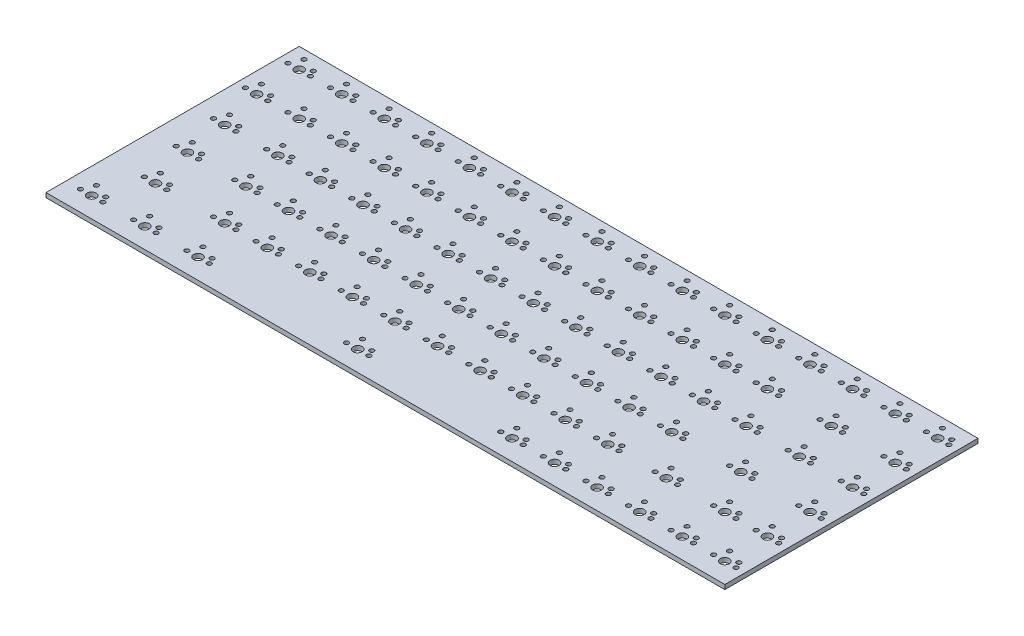
SolidWorks part; units mm, degrees
ref_plane "Спереди" through (0, 0, 0) normal (0, 0, 1) x (1, 0, 0)
ref_plane "Сверху" through (0, 0, 0) normal (0, 1, 0) x (1, 0, 0)
ref_plane "Справа" through (0, 0, 0) normal (1, 0, 0) x (0, 0, -1)
sketch "Эскиз1" plane through (0, 0, 0) normal (0, 1, 0) x (1, 0, 0)
  line L1 (-9, 9) -> (294, 9)
  line L2 (-9, 9) -> (-9, -104)
  line L3 (-9, -104) -> (294, -104)
  line L4 (294, 9) -> (294, -104)
  circle A0 centre (-2.8676, 5) radius 1
  circle A6 centre (0, 0) radius 2
  circle A7 centre (-5, 0) radius 1
  circle A8 centre (5, 0) radius 1
  circle A9 centre (3.65, 2.6) radius 1
  circle A10 centre (16.1324, 5) radius 1
  circle A11 centre (19, 0) radius 2
  circle A12 centre (14, 0) radius 1
  circle A13 centre (24, 0) radius 1
  circle A14 centre (22.65, 2.6) radius 1
  circle A15 centre (16.1324, -14) radius 1
  circle A16 centre (19, -19) radius 2
  circle A17 centre (14, -19) radius 1
  circle A18 centre (24, -19) radius 1
  circle A19 centre (22.65, -16.4) radius 1
  circle A20 centre (-2.8676, -14) radius 1
  circle A21 centre (0, -19) radius 2
  circle A22 centre (-5, -19) radius 1
  circle A23 centre (5, -19) radius 1
  circle A24 centre (3.65, -16.4) radius 1
  circle A25 centre (35.1324, 5) radius 1
  circle A26 centre (38, 0) radius 2
  circle A27 centre (33, 0) radius 1
  circle A28 centre (43, 0) radius 1
  circle A29 centre (41.65, 2.6) radius 1
  circle A30 centre (35.1324, -14) radius 1
  circle A31 centre (38, -19) radius 2
  circle A32 centre (33, -19) radius 1
  circle A33 centre (43, -19) radius 1
  circle A34 centre (41.65, -16.4) radius 1
  circle A35 centre (54.1324, 5) radius 1
  circle A36 centre (57, 0) radius 2
  circle A37 centre (52, 0) radius 1
  circle A38 centre (62, 0) radius 1
  circle A39 centre (60.65, 2.6) radius 1
  circle A40 centre (54.1324, -14) radius 1
  circle A41 centre (57, -19) radius 2
  circle A42 centre (52, -19) radius 1
  circle A43 centre (62, -19) radius 1
  circle A44 centre (60.65, -16.4) radius 1
  circle A45 centre (73.1324, 5) radius 1
  circle A46 centre (76, 0) radius 2
  circle A47 centre (71, 0) radius 1
  circle A48 centre (81, 0) radius 1
  circle A49 centre (79.65, 2.6) radius 1
  circle A50 centre (92.1324, 5) radius 1
  circle A51 centre (95, 0) radius 2
  circle A52 centre (90, 0) radius 1
  circle A53 centre (100, 0) radius 1
  circle A54 centre (98.65, 2.6) radius 1
  circle A55 centre (111.1324, 5) radius 1
  circle A56 centre (114, 0) radius 2
  circle A57 centre (109, 0) radius 1
  circle A58 centre (119, 0) radius 1
  circle A59 centre (117.65, 2.6) radius 1
  circle A60 centre (130.1324, 5) radius 1
  circle A61 centre (133, 0) radius 2
  circle A62 centre (128, 0) radius 1
  circle A63 centre (138, 0) radius 1
  circle A64 centre (136.65, 2.6) radius 1
  circle A65 centre (149.1324, 5) radius 1
  circle A66 centre (152, 0) radius 2
  circle A67 centre (147, 0) radius 1
  circle A68 centre (157, 0) radius 1
  circle A69 centre (155.65, 2.6) radius 1
  circle A70 centre (168.1324, 5) radius 1
  circle A71 centre (171, 0) radius 2
  circle A72 centre (166, 0) radius 1
  circle A73 centre (176, 0) radius 1
  circle A74 centre (174.65, 2.6) radius 1
  circle A75 centre (187.1324, 5) radius 1
  circle A76 centre (190, 0) radius 2
  circle A77 centre (185, 0) radius 1
  circle A78 centre (195, 0) radius 1
  circle A79 centre (193.65, 2.6) radius 1
  circle A80 centre (187.1324, -14) radius 1
  circle A81 centre (190, -19) radius 2
  circle A82 centre (185, -19) radius 1
  circle A83 centre (195, -19) radius 1
  circle A84 centre (193.65, -16.4) radius 1
  circle A85 centre (168.1324, -14) radius 1
  circle A86 centre (171, -19) radius 2
  circle A87 centre (166, -19) radius 1
  circle A88 centre (176, -19) radius 1
  circle A89 centre (174.65, -16.4) radius 1
  circle A90 centre (149.1324, -14) radius 1
  circle A91 centre (152, -19) radius 2
  circle A92 centre (147, -19) radius 1
  circle A93 centre (157, -19) radius 1
  circle A94 centre (155.65, -16.4) radius 1
  circle A95 centre (130.1324, -14) radius 1
  circle A96 centre (133, -19) radius 2
  circle A97 centre (128, -19) radius 1
  circle A98 centre (138, -19) radius 1
  circle A99 centre (136.65, -16.4) radius 1
  circle A100 centre (111.1324, -14) radius 1
  circle A101 centre (114, -19) radius 2
  circle A102 centre (109, -19) radius 1
  circle A103 centre (119, -19) radius 1
  circle A104 centre (117.65, -16.4) radius 1
  circle A105 centre (92.1324, -14) radius 1
  circle A106 centre (95, -19) radius 2
  circle A107 centre (90, -19) radius 1
  circle A108 centre (100, -19) radius 1
  circle A109 centre (98.65, -16.4) radius 1
  circle A110 centre (73.1324, -14) radius 1
  circle A111 centre (76, -19) radius 2
  circle A112 centre (71, -19) radius 1
  circle A113 centre (81, -19) radius 1
  circle A114 centre (79.65, -16.4) radius 1
  circle A115 centre (196.6324, -33) radius 1
  circle A116 centre (199.5, -38) radius 2
  circle A117 centre (194.5, -38) radius 1
  circle A118 centre (204.5, -38) radius 1
  circle A119 centre (203.15, -35.4) radius 1
  circle A120 centre (177.6324, -33) radius 1
  circle A121 centre (180.5, -38) radius 2
  circle A122 centre (175.5, -38) radius 1
  circle A123 centre (185.5, -38) radius 1
  circle A124 centre (184.15, -35.4) radius 1
  circle A125 centre (158.6324, -33) radius 1
  circle A126 centre (161.5, -38) radius 2
  circle A127 centre (156.5, -38) radius 1
  circle A128 centre (166.5, -38) radius 1
  circle A129 centre (165.15, -35.4) radius 1
  circle A130 centre (139.6324, -33) radius 1
  circle A131 centre (142.5, -38) radius 2
  circle A132 centre (137.5, -38) radius 1
  circle A133 centre (147.5, -38) radius 1
  circle A134 centre (146.15, -35.4) radius 1
  circle A135 centre (120.6324, -33) radius 1
  circle A136 centre (123.5, -38) radius 2
  circle A137 centre (118.5, -38) radius 1
  circle A138 centre (128.5, -38) radius 1
  circle A139 centre (127.15, -35.4) radius 1
  circle A140 centre (101.6324, -33) radius 1
  circle A141 centre (104.5, -38) radius 2
  circle A142 centre (99.5, -38) radius 1
  circle A143 centre (109.5, -38) radius 1
  circle A144 centre (108.15, -35.4) radius 1
  circle A145 centre (82.6324, -33) radius 1
  circle A146 centre (85.5, -38) radius 2
  circle A147 centre (80.5, -38) radius 1
  circle A148 centre (90.5, -38) radius 1
  circle A149 centre (89.15, -35.4) radius 1
  circle A150 centre (63.6324, -33) radius 1
  circle A151 centre (66.5, -38) radius 2
  circle A152 centre (61.5, -38) radius 1
  circle A153 centre (71.5, -38) radius 1
  circle A154 centre (70.15, -35.4) radius 1
  circle A155 centre (44.6324, -33) radius 1
  circle A156 centre (47.5, -38) radius 2
  circle A157 centre (42.5, -38) radius 1
  circle A158 centre (52.5, -38) radius 1
  circle A159 centre (51.15, -35.4) radius 1
  circle A160 centre (25.6324, -33) radius 1
  circle A161 centre (28.5, -38) radius 2
  circle A162 centre (23.5, -38) radius 1
  circle A163 centre (33.5, -38) radius 1
  circle A164 centre (32.15, -35.4) radius 1
  circle A165 centre (1.8824, -33) radius 1
  circle A166 centre (4.75, -38) radius 2
  circle A167 centre (-0.25, -38) radius 1
  circle A168 centre (9.75, -38) radius 1
  circle A169 centre (8.4, -35.4) radius 1
  circle A170 centre (4.2574, -52) radius 1
  circle A171 centre (7.125, -57) radius 2
  circle A172 centre (2.125, -57) radius 1
  circle A173 centre (12.125, -57) radius 1
  circle A174 centre (10.775, -54.4) radius 1
  circle A175 centre (30.3824, -52) radius 1
  circle A176 centre (33.25, -57) radius 2
  circle A177 centre (28.25, -57) radius 1
  circle A178 centre (38.25, -57) radius 1
  circle A179 centre (36.9, -54.4) radius 1
  circle A180 centre (49.3824, -52) radius 1
  circle A181 centre (52.25, -57) radius 2
  circle A182 centre (47.25, -57) radius 1
  circle A183 centre (57.25, -57) radius 1
  circle A184 centre (55.9, -54.4) radius 1
  circle A185 centre (68.3824, -52) radius 1
  circle A186 centre (71.25, -57) radius 2
  circle A187 centre (66.25, -57) radius 1
  circle A188 centre (76.25, -57) radius 1
  circle A189 centre (74.9, -54.4) radius 1
  circle A190 centre (87.3824, -52) radius 1
  circle A191 centre (90.25, -57) radius 2
  circle A192 centre (85.25, -57) radius 1
  circle A193 centre (95.25, -57) radius 1
  circle A194 centre (93.9, -54.4) radius 1
  circle A195 centre (106.3824, -52) radius 1
  circle A196 centre (109.25, -57) radius 2
  circle A197 centre (104.25, -57) radius 1
  circle A198 centre (114.25, -57) radius 1
  circle A199 centre (112.9, -54.4) radius 1
  circle A200 centre (125.3824, -52) radius 1
  circle A201 centre (128.25, -57) radius 2
  circle A202 centre (123.25, -57) radius 1
  circle A203 centre (133.25, -57) radius 1
  circle A204 centre (131.9, -54.4) radius 1
  circle A205 centre (144.3824, -52) radius 1
  circle A206 centre (147.25, -57) radius 2
  circle A207 centre (142.25, -57) radius 1
  circle A208 centre (152.25, -57) radius 1
  circle A209 centre (150.9, -54.4) radius 1
  circle A210 centre (163.3824, -52) radius 1
  circle A211 centre (166.25, -57) radius 2
  circle A212 centre (161.25, -57) radius 1
  circle A213 centre (171.25, -57) radius 1
  circle A214 centre (169.9, -54.4) radius 1
  circle A215 centre (182.3824, -52) radius 1
  circle A216 centre (185.25, -57) radius 2
  circle A217 centre (180.25, -57) radius 1
  circle A218 centre (190.25, -57) radius 1
  circle A219 centre (188.9, -54.4) radius 1
  circle A220 centre (201.3824, -52) radius 1
  circle A221 centre (204.25, -57) radius 2
  circle A222 centre (199.25, -57) radius 1
  circle A223 centre (209.25, -57) radius 1
  circle A224 centre (207.9, -54.4) radius 1
  circle A225 centre (191.8824, -71) radius 1
  circle A226 centre (194.75, -76) radius 2
  circle A227 centre (189.75, -76) radius 1
  circle A228 centre (199.75, -76) radius 1
  circle A229 centre (198.4, -73.4) radius 1
  circle A230 centre (172.8824, -71) radius 1
  circle A231 centre (175.75, -76) radius 2
  circle A232 centre (170.75, -76) radius 1
  circle A233 centre (180.75, -76) radius 1
  circle A234 centre (179.4, -73.4) radius 1
  circle A235 centre (153.8824, -71) radius 1
  circle A236 centre (156.75, -76) radius 2
  circle A237 centre (151.75, -76) radius 1
  circle A238 centre (161.75, -76) radius 1
  circle A239 centre (160.4, -73.4) radius 1
  circle A240 centre (134.8824, -71) radius 1
  circle A241 centre (137.75, -76) radius 2
  circle A242 centre (132.75, -76) radius 1
  circle A243 centre (142.75, -76) radius 1
  circle A244 centre (141.4, -73.4) radius 1
  circle A245 centre (115.8824, -71) radius 1
  circle A246 centre (118.75, -76) radius 2
  circle A247 centre (113.75, -76) radius 1
  circle A248 centre (123.75, -76) radius 1
  circle A249 centre (122.4, -73.4) radius 1
  circle A250 centre (96.8824, -71) radius 1
  circle A251 centre (99.75, -76) radius 2
  circle A252 centre (94.75, -76) radius 1
  circle A253 centre (104.75, -76) radius 1
  circle A254 centre (103.4, -73.4) radius 1
  circle A255 centre (77.8824, -71) radius 1
  circle A256 centre (80.75, -76) radius 2
  circle A257 centre (75.75, -76) radius 1
  circle A258 centre (85.75, -76) radius 1
  circle A259 centre (84.4, -73.4) radius 1
  circle A260 centre (58.8824, -71) radius 1
  circle A261 centre (61.75, -76) radius 2
  circle A262 centre (56.75, -76) radius 1
  circle A263 centre (66.75, -76) radius 1
  circle A264 centre (65.4, -73.4) radius 1
  circle A265 centre (39.8824, -71) radius 1
  circle A266 centre (42.75, -76) radius 2
  circle A267 centre (37.75, -76) radius 1
  circle A268 centre (47.75, -76) radius 1
  circle A269 centre (46.4, -73.4) radius 1
  circle A270 centre (9.0074, -71) radius 1
  circle A271 centre (11.875, -76) radius 2
  circle A272 centre (6.875, -76) radius 1
  circle A273 centre (16.875, -76) radius 1
  circle A274 centre (15.525, -73.4) radius 1
  circle A275 centre (206.1324, 5) radius 1
  circle A276 centre (209, 0) radius 2
  circle A277 centre (204, 0) radius 1
  circle A278 centre (214, 0) radius 1
  circle A279 centre (212.65, 2.6) radius 1
  circle A280 centre (225.1324, 5) radius 1
  circle A281 centre (228, 0) radius 2
  circle A282 centre (223, 0) radius 1
  circle A283 centre (233, 0) radius 1
  circle A284 centre (231.65, 2.6) radius 1
  circle A285 centre (244.1324, 5) radius 1
  circle A286 centre (247, 0) radius 2
  circle A287 centre (242, 0) radius 1
  circle A288 centre (252, 0) radius 1
  circle A289 centre (250.65, 2.6) radius 1
  circle A290 centre (263.1324, 5) radius 1
  circle A291 centre (266, 0) radius 2
  circle A292 centre (261, 0) radius 1
  circle A293 centre (271, 0) radius 1
  circle A294 centre (269.65, 2.6) radius 1
  circle A295 centre (282.1324, 5) radius 1
  circle A296 centre (285, 0) radius 2
  circle A297 centre (280, 0) radius 1
  circle A298 centre (290, 0) radius 1
  circle A299 centre (288.65, 2.6) radius 1
  circle A300 centre (282.1324, -14) radius 1
  circle A301 centre (285, -19) radius 2
  circle A302 centre (280, -19) radius 1
  circle A303 centre (290, -19) radius 1
  circle A304 centre (288.65, -16.4) radius 1
  circle A305 centre (253.6324, -14) radius 1
  circle A306 centre (256.5, -19) radius 2
  circle A307 centre (251.5, -19) radius 1
  circle A308 centre (261.5, -19) radius 1
  circle A309 centre (260.15, -16.4) radius 1
  circle A310 centre (225.1324, -14) radius 1
  circle A311 centre (228, -19) radius 2
  circle A312 centre (223, -19) radius 1
  circle A313 centre (233, -19) radius 1
  circle A314 centre (231.65, -16.4) radius 1
  circle A315 centre (206.1324, -14) radius 1
  circle A316 centre (209, -19) radius 2
  circle A317 centre (204, -19) radius 1
  circle A318 centre (214, -19) radius 1
  circle A319 centre (212.65, -16.4) radius 1
  circle A320 centre (215.6324, -33) radius 1
  circle A321 centre (218.5, -38) radius 2
  circle A322 centre (213.5, -38) radius 1
  circle A323 centre (223.5, -38) radius 1
  circle A324 centre (222.15, -35.4) radius 1
  circle A325 centre (234.6324, -33) radius 1
  circle A326 centre (237.5, -38) radius 2
  circle A327 centre (232.5, -38) radius 1
  circle A328 centre (242.5, -38) radius 1
  circle A329 centre (241.15, -35.4) radius 1
  circle A330 centre (258.3824, -33) radius 1
  circle A331 centre (261.25, -38) radius 2
  circle A332 centre (256.25, -38) radius 1
  circle A333 centre (266.25, -38) radius 1
  circle A334 centre (264.9, -35.4) radius 1
  circle A335 centre (282.1324, -33) radius 1
  circle A336 centre (285, -38) radius 2
  circle A337 centre (280, -38) radius 1
  circle A338 centre (290, -38) radius 1
  circle A339 centre (288.65, -35.4) radius 1
  circle A340 centre (282.1324, -52) radius 1
  circle A341 centre (285, -57) radius 2
  circle A342 centre (280, -57) radius 1
  circle A343 centre (290, -57) radius 1
  circle A344 centre (288.65, -54.4) radius 1
  circle A345 centre (251.2574, -52) radius 1
  circle A346 centre (254.125, -57) radius 2
  circle A347 centre (249.125, -57) radius 1
  circle A348 centre (259.125, -57) radius 1
  circle A349 centre (257.775, -54.4) radius 1
  circle A350 centre (220.3824, -52) radius 1
  circle A351 centre (223.25, -57) radius 2
  circle A352 centre (218.25, -57) radius 1
  circle A353 centre (228.25, -57) radius 1
  circle A354 centre (226.9, -54.4) radius 1
  circle A355 centre (210.8824, -71) radius 1
  circle A356 centre (213.75, -76) radius 2
  circle A357 centre (208.75, -76) radius 1
  circle A358 centre (218.75, -76) radius 1
  circle A359 centre (217.4, -73.4) radius 1
  circle A360 centre (237.0074, -71) radius 1
  circle A361 centre (239.875, -76) radius 2
  circle A362 centre (234.875, -76) radius 1
  circle A363 centre (244.875, -76) radius 1
  circle A364 centre (243.525, -73.4) radius 1
  circle A365 centre (263.1324, -71) radius 1
  circle A366 centre (266, -76) radius 2
  circle A367 centre (261, -76) radius 1
  circle A368 centre (271, -76) radius 1
  circle A369 centre (269.65, -73.4) radius 1
  circle A370 centre (282.1324, -71) radius 1
  circle A371 centre (285, -76) radius 2
  circle A372 centre (280, -76) radius 1
  circle A373 centre (290, -76) radius 1
  circle A374 centre (288.65, -73.4) radius 1
  circle A375 centre (282.1324, -90) radius 1
  circle A376 centre (285, -95) radius 2
  circle A377 centre (280, -95) radius 1
  circle A378 centre (290, -95) radius 1
  circle A379 centre (288.65, -92.4) radius 1
  circle A380 centre (263.1324, -90) radius 1
  circle A381 centre (266, -95) radius 2
  circle A382 centre (261, -95) radius 1
  circle A383 centre (271, -95) radius 1
  circle A384 centre (269.65, -92.4) radius 1
  circle A385 centre (244.1324, -90) radius 1
  circle A386 centre (247, -95) radius 2
  circle A387 centre (242, -95) radius 1
  circle A388 centre (252, -95) radius 1
  circle A389 centre (250.65, -92.4) radius 1
  circle A390 centre (225.1324, -90) radius 1
  circle A391 centre (228, -95) radius 2
  circle A392 centre (223, -95) radius 1
  circle A393 centre (233, -95) radius 1
  circle A394 centre (231.65, -92.4) radius 1
  circle A395 centre (206.1324, -90) radius 1
  circle A396 centre (209, -95) radius 2
  circle A397 centre (204, -95) radius 1
  circle A398 centre (214, -95) radius 1
  circle A399 centre (212.65, -92.4) radius 1
  circle A400 centre (187.1324, -90) radius 1
  circle A401 centre (190, -95) radius 2
  circle A402 centre (185, -95) radius 1
  circle A403 centre (195, -95) radius 1
  circle A404 centre (193.65, -92.4) radius 1
  circle A405 centre (47.0074, -90) radius 1
  circle A406 centre (49.875, -95) radius 2
  circle A407 centre (44.875, -95) radius 1
  circle A408 centre (54.875, -95) radius 1
  circle A409 centre (53.525, -92.4) radius 1
  circle A410 centre (23.2574, -90) radius 1
  circle A411 centre (26.125, -95) radius 2
  circle A412 centre (21.125, -95) radius 1
  circle A413 centre (31.125, -95) radius 1
  circle A414 centre (29.775, -92.4) radius 1
  circle A415 centre (-0.4926, -90) radius 1
  circle A416 centre (2.375, -95) radius 2
  circle A417 centre (-2.625, -95) radius 1
  circle A418 centre (7.375, -95) radius 1
  circle A419 centre (6.025, -92.4) radius 1
  circle A420 centre (118.2574, -90) radius 1
  circle A421 centre (121.125, -95) radius 2
  circle A422 centre (116.125, -95) radius 1
  circle A423 centre (126.125, -95) radius 1
  circle A424 centre (124.775, -92.4) radius 1
  point P0 (0, 0)
  point P1 (266, -19)
  point P3 (247, -19)
  point P5 (19, 0)
  point P6 (38, 0)
  point P7 (57, 0)
  point P8 (76, 0)
  point P9 (95, 0)
  point P10 (114, 0)
  point P11 (133, 0)
  point P12 (152, 0)
  point P13 (171, 0)
  point P14 (190, 0)
  point P15 (209, 0)
  point P16 (228, 0)
  point P17 (247, 0)
  point P18 (266, 0)
  point P19 (285, 0)
  point P20 (19, -19)
  point P21 (38, -19)
  point P22 (57, -19)
  point P23 (76, -19)
  point P24 (95, -19)
  point P25 (114, -19)
  point P26 (133, -19)
  point P27 (152, -19)
  point P28 (171, -19)
  point P29 (190, -19)
  point P30 (209, -19)
  point P31 (228, -19)
  point P32 (266, -76)
  point P33 (285, -38)
  point P34 (285, -19)
  point P35 (0, -19)
  point P36 (285, -57)
  point P37 (285, -76)
  point P38 (285, -95)
  point P39 (266, -95)
  point P40 (247, -95)
  point P41 (228, -95)
  point P42 (209, -95)
  point P43 (190, -95)
  point P47 (4.75, -38)
  point P48 (7.125, -57)
  point P49 (11.875, -76)
  point P50 (2.375, -95)
  point P51 (42.75, -76)
  point P52 (26.125, -95)
  point P53 (49.875, -95)
  point P54 (33.25, -57)
  point P55 (28.5, -38)
  point P56 (261.25, -38)
  point P57 (61.75, -76)
  point P58 (47.5, -38)
  point P59 (66.5, -38)
  point P60 (85.5, -38)
  point P61 (104.5, -38)
  point P62 (123.5, -38)
  point P63 (142.5, -38)
  point P64 (161.5, -38)
  point P65 (180.5, -38)
  point P66 (199.5, -38)
  point P67 (218.5, -38)
  point P68 (237.5, -38)
  point P69 (52.25, -57)
  point P70 (71.25, -57)
  point P71 (90.25, -57)
  point P72 (109.25, -57)
  point P73 (128.25, -57)
  point P74 (147.25, -57)
  point P75 (166.25, -57)
  point P76 (185.25, -57)
  point P77 (204.25, -57)
  point P78 (223.25, -57)
  point P79 (80.75, -76)
  point P80 (99.75, -76)
  point P81 (118.75, -76)
  point P82 (137.75, -76)
  point P83 (156.75, -76)
  point P84 (175.75, -76)
  point P85 (194.75, -76)
  point P86 (213.75, -76)
  point P87 (254.125, -57)
  point P88 (239.875, -76)
  point P89 (256.5, -19)
  point P90 (121.125, -95)
  dimension "D6" = 19
  dimension "D7" = 113
  dimension "D8" = 19
  dimension "D9" = 9
  dimension "D10" = 9
  dimension "D11" = 303
  dimension "D12" = 13.75
  dimension "D13" = 16.125
  dimension "D14" = 20.875
  dimension "D15" = 11.375
  dimension "D17" = 23.75
  dimension "D18" = 26.125
  dimension "D19" = 30.875
  dimension "D23" = 23.75
  dimension "D24" = 23.75
  dimension "D25" = 71.25
  dimension "D26" = 28
  dimension "D27" = 9
  dimension "D28" = 9
  dimension "D29" = 9
  dimension "D30" = 28.5
  dimension "D31" = 23.75
  dimension "D32" = 30.875
  dimension "D33" = 26.125
  dimension "D1" = 16
  dimension "D2" = 2
  dimension "D3" = 5
  dimension "D4" = 2
  dimension "D5" = 6
  dimension "D16" = 3
  dimension "D20" = 12
  dimension "D21" = 11
  dimension "D22" = 10
extrude "Бобышка-Вытянуть1" add sketch "Эскиз1" along normal blind 2
